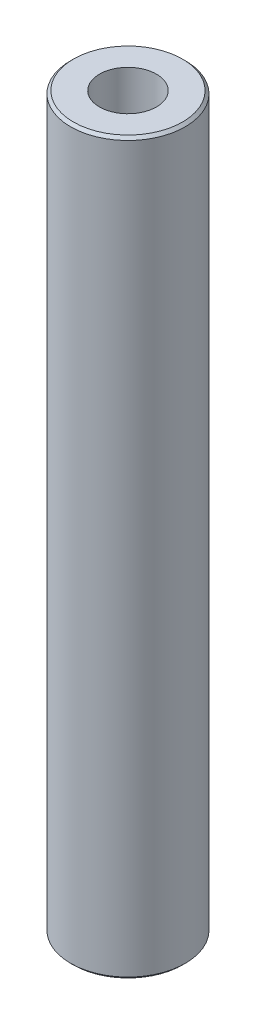
SolidWorks part; units mm, degrees
ref_plane "Front Plane" through (0, 0, 0) normal (0, 0, 1) x (1, 0, 0)
ref_plane "Top Plane" through (0, 0, 0) normal (0, 1, 0) x (1, 0, 0)
ref_plane "Right Plane" through (0, 0, 0) normal (1, 0, 0) x (0, 0, -1)
sketch "Sketch1" plane through (0, 0, 0) normal (0, 1, 0) x (1, 0, 0)
  circle A0 centre (0, 0) radius 20
  dimension "SHAFT_OD" = 40
extrude "Boss-Extrude1" add sketch "Sketch1" along normal blind 254.7476
sketch "Sketch2" plane through (0, 0, 0) normal (0, 1, 0) x (1, 0, 0)
  circle A0 centre (0, 0) radius 9.9379
  dimension "BORE_D" = 19.8758
extrude "Cut-Extrude1" cut sketch "Sketch2" along normal through all
chamfer "Chamfer1" distance 0.9641 angle 45 2 edges at (0, 254.7476, 20) (0, 0, 20)
